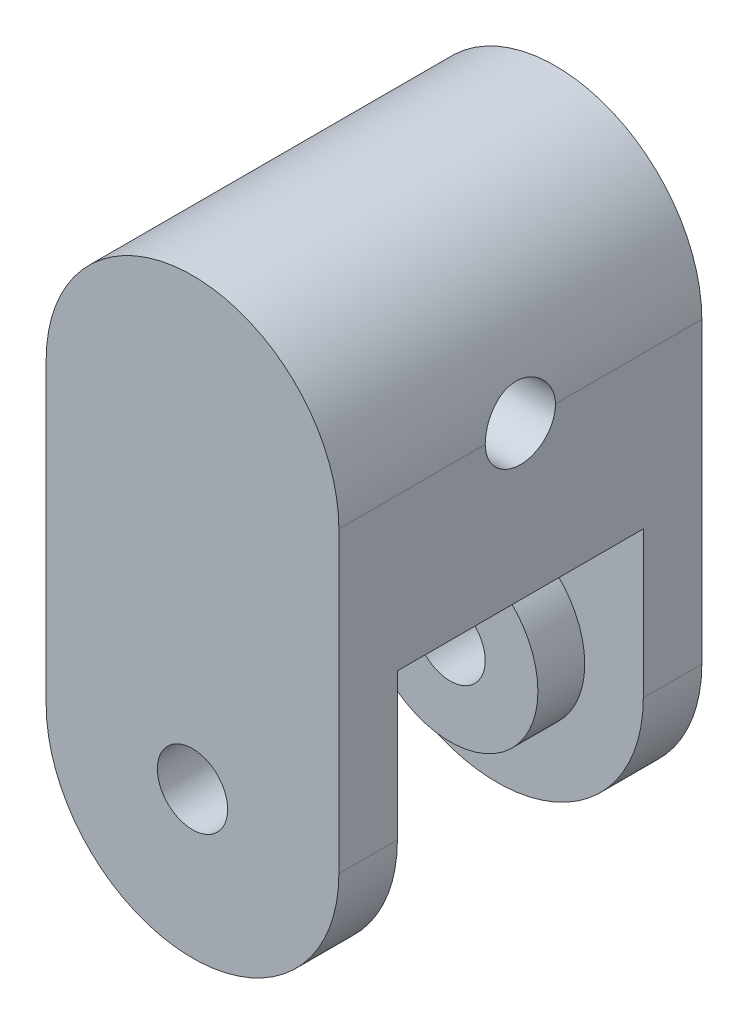
SolidWorks part; units mm, degrees
ref_plane "Front Plane" through (0, 0, 0) normal (0, 0, 1) x (1, 0, 0)
ref_plane "Top Plane" through (0, 0, 0) normal (0, 1, 0) x (1, 0, 0)
ref_plane "Right Plane" through (0, 0, 0) normal (1, 0, 0) x (0, 0, -1)
sketch "Sketch1" plane through (0, 0, 0) normal (0, 0, 1) x (1, 0, 0)
  line L0 (-12.5, 0) -> (-12.5, 12.5)
  line L1 (-12.5, 12.5) -> (12.5, 12.5)
  line L2 (12.5, 12.5) -> (12.5, 0)
  arc A0 (-12.5, 0) -> (12.5, 0) centre (0, 0) ccw
  dimension "D1" = 25
extrude "Boss-Extrude2" add sketch "Sketch1" along normal mid plane 31
sketch "Sketch5" plane through (0, 0, 0) normal (0, 1, 0) x (1, 0, 0)
  line L0 (0, 0) -> (0, 10.5) construction
  line L1 (0, 0) -> (12.5, 0) construction
  line L3 (12.5, 10.5) -> (-12.5, 10.5)
  line L5 (12.5, -10.5) -> (-12.5, -10.5)
  line L6 (-12.5, 10.5) -> (-12.5, -10.5)
  line L7 (12.5, 10.5) -> (12.5, -10.5)
  line L8 (-12.5, -15.5) -> (-12.5, 15.5) construction
  point P8 (0, 0)
  point P9 (-12.5, 10.5)
  point P10 (0, 10.5)
  point P15 (0, 0)
  dimension "D1" = 10.5
extrude "Cut-Extrude1" cut sketch "Sketch5" against normal through all both and the other way through all contours L7 L5 L6 L3
sketch "Sketch6" plane through (0, 0, -10.5) normal (0, 0, 1) x (1, 0, 0)
  circle A0 centre (0, 0) radius 7.5
  dimension "D1" = 15
extrude "Boss-Extrude3" add sketch "Sketch6" along normal blind 4
sketch "Sketch7" plane through (0, 0, 10.5) normal (0, 0, -1) x (-1, 0, 0)
  circle A0 centre (0, 0) radius 7.5
  dimension "D1" = 15
extrude "Boss-Extrude4" add sketch "Sketch7" along normal blind 4
sketch "Sketch8" plane through (0, 0, -15.5) normal (0, 0, -1) x (-1, 0, 0)
  circle A0 centre (0, 0) radius 3
  dimension "D1" = 6
extrude "Cut-Extrude2" cut sketch "Sketch8" against normal through all both and the other way through all
sketch "Sketch9" plane through (0, 0, 15.5) normal (0, 0, 1) x (1, 0, 0)
  line L0 (12.5, 12.5) -> (12.5, 25.5)
  line L2 (-12.5, 25.5) -> (-12.5, 12.5)
  line L3 (0, 0) -> (0, 12.5) construction
  line L4 (12.5, 12.5) -> (-12.5, 12.5) construction
  line L5 (-12.5, 12.5) -> (12.5, 12.5)
  line L6 (-12.5, 12.5) -> (-12.5, 0) construction
  line L7 (0, 22.5) -> (0, 12.5) construction
  circle A0 centre (0, 0) radius 12.5 construction
  arc A2 (12.5, 25.5) -> (-12.5, 25.5) centre (0, 25.5) ccw
  circle A4 centre (0, 25.5) radius 3 construction
  dimension "D1" = 6
  dimension "D2" = 10
extrude "Boss-Extrude6" add sketch "Sketch9" against normal up to surface (31 mm away) up to face at (3, 0, -15.5)
sketch "Sketch11" plane through (12.5, 0, 0) normal (1, 0, 0) x (0, 0, -1)
  line L1 (0, 22.5) -> (0, 12.5) construction
  line L2 (15.5, 12.5) -> (-10.5, 12.5) construction
  circle A0 centre (0, 25.5) radius 3
  dimension "D2" = 6
  dimension "D1" = 10
extrude "Cut-Extrude3" cut sketch "Sketch11" against normal through all both and the other way through all contours A0
combine bodies "Combine1" operation type add bodies to combine 107 112
